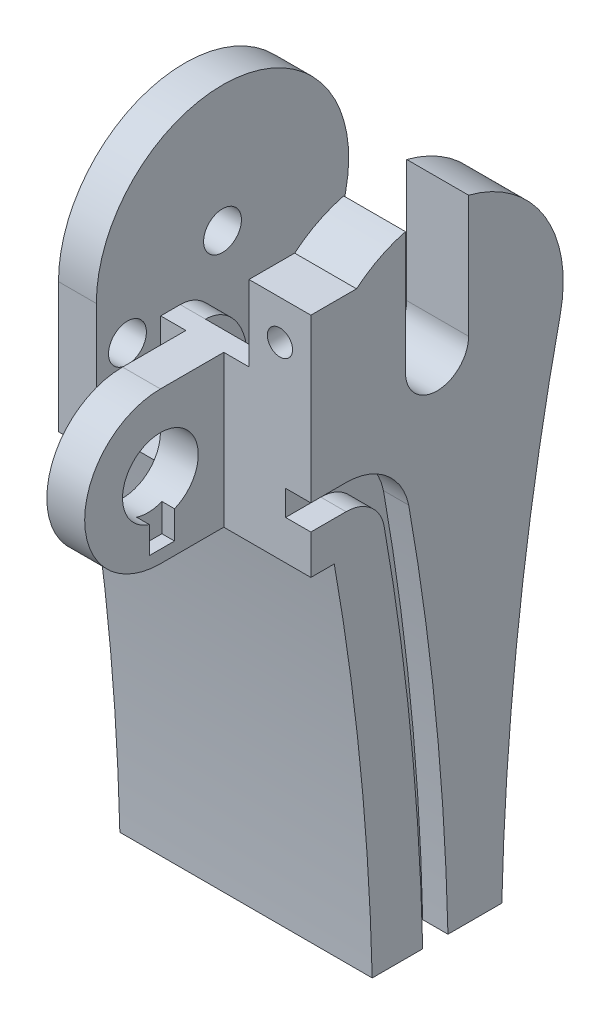
SolidWorks part; units mm, degrees
ref_plane "Front Plane" through (0, 0, 0) normal (0, 0, 1) x (1, 0, 0)
ref_plane "Top Plane" through (0, 0, 0) normal (0, 1, 0) x (1, 0, 0)
ref_plane "Right Plane" through (0, 0, 0) normal (1, 0, 0) x (0, 0, -1)
sketch "Sketch1" plane through (0, 0, 0) normal (1, 0, 0) x (0, 0, -1)
  arc A0 (9.7654, 20.1165) -> (-9.7654, 20.1165) centre (0, 22.2701) ccw
  arc A1 (-7.8874, -56.3924) -> (7.8874, -56.3924) centre (0, -57.7299) ccw
  arc A2 (-7.8874, -56.3924) -> (-9.7654, 20.1165) centre (-205.0724, -22.9549) ccw
  circle A3 centre (0, 22.2701) radius 1.5
  arc A4 (9.7654, 20.1165) -> (7.8874, -56.3924) centre (205.0724, -22.9549) ccw
  circle A5 centre (0, -57.7299) radius 2.5
extrude "Boss-Extrude1" add sketch "Sketch1" along normal blind 20
sketch "Sketch2" plane through (0, 0, 0) normal (0, 0, 1) x (1, 0, 0)
  line L1 (0, -65.7299) -> (8.1, -65.7299)
  line L2 (0, -65.7299) -> (0, -45.7299)
  line L3 (0, -45.7299) -> (8.1, -45.7299)
  line L4 (8.1, -65.7299) -> (8.1, -45.7299)
  line L5 (20, -65.7299) -> (14.8, -65.7299)
  line L6 (20, -65.7299) -> (20, -45.7299)
  line L7 (20, -45.7299) -> (14.8, -45.7299)
  line L8 (14.8, -65.7299) -> (14.8, -45.7299)
  line L11 (3, 32.2701) -> (8.1, 32.2701)
  line L12 (3, 32.2701) -> (3, 12.2701)
  line L13 (3, 12.2701) -> (8.1, 12.2701)
  line L14 (8.1, 32.2701) -> (8.1, 12.2701)
extrude "Cut-Extrude1" cut sketch "Sketch2" against normal blind 20 and the other way blind 20
sketch "Sketch3" plane through (8.1, 0, 0) normal (-1, 0, 0) x (0, 0, 1)
  line L0 (8.5, 22.2701) -> (8.5, 40.9095)
  line L1 (8.5, 40.9095) -> (-17.5287, 40.9095)
  line L2 (-17.5287, 40.9095) -> (-17.5287, 13.7701)
  line L3 (0, 13.7701) -> (-17.5287, 13.7701)
  arc A0 (0, 13.7701) -> (8.5, 22.2701) centre (0, 22.2701) ccw
extrude "Cut-Extrude2" cut sketch "Sketch3" against normal blind 9
sketch "Sketch4" plane through (8.1, 0, 0) normal (-1, 0, 0) x (0, 0, 1)
  line L0 (8.5, 27.5379) -> (8.2838, 12.7416)
  line L1 (8.2838, 12.7416) -> (10.2838, 12.7416)
  line L2 (10.2838, 12.7416) -> (10.2838, 27.5379)
  line L3 (10.2838, 27.5379) -> (8.5, 27.5379)
  arc A0 (9.7654, 20.1165) -> (6.3734, -45.7299) centre (205.0724, -22.9549) ccw construction
extrude "Boss-Extrude2" add sketch "Sketch4" against normal through all
sketch "Sketch5" plane through (8.1, 0, 0) normal (-1, 0, 0) x (0, 0, 1)
  line L4 (8.1452, 11.9686) -> (8.4478, 23.9686)
  line L6 (15.0224, 23.9686) -> (9.8547, 23.9686)
  line L8 (8.1452, 11.9686) -> (15.0224, 11.9686)
  line L9 (8.5, 27.5379) -> (8.4045, 20.9993) construction
  line L10 (8.4478, 23.9686) -> (9.8547, 23.9686)
  circle A2 centre (15.0224, 17.9686) radius 3
  arc A5 (15.0224, 11.9686) -> (15.0224, 23.9686) centre (15.0224, 17.9686) ccw
  arc A6 (9.7654, 20.1165) -> (-9.7654, 20.1165) centre (0, 22.2701) ccw construction
  arc A7 (9.7654, 20.1165) -> (6.3734, -45.7299) centre (205.0724, -22.9549) ccw construction
extrude "Boss-Extrude3" add sketch "Sketch5" against normal blind 5
sketch "Sketch12" plane through (13.1, 0, 0) normal (1, 0, 0) x (0, 0, -1)
  line L2 (-13.9029, 14.9686) -> (-13.9029, 12.9686)
  line L4 (-15.9029, 14.9686) -> (-15.9029, 15.2943)
  line L5 (-15.9029, 15.2943) -> (-13.9029, 15.2943)
  line L6 (-13.9029, 12.9686) -> (-15.9029, 12.9686)
  line L7 (-13.9029, 14.9686) -> (-13.9029, 15.2943)
  line L11 (-15.9029, 14.9686) -> (-15.9029, 12.9686)
extrude "Cut-Extrude6" cut sketch "Sketch12" against normal blind 1
sketch "Sketch13" plane through (17.1, 0, 0) normal (-1, 0, 0) x (0, 0, 1)
  circle A0 centre (0, 22.2701) radius 2.5
extrude "Cut-Extrude7" cut sketch "Sketch13" against normal blind 4
sketch "Sketch15" plane through (0, 0, 0) normal (-1, 0, 0) x (0, 0, 1)
  line L0 (10, 22.2701) -> (10, 11.9686)
  line L1 (8.1452, 11.9686) -> (15.0224, 11.9686) construction
  line L2 (10, 11.9686) -> (8.1452, 11.9686)
  line L3 (10, 22.2701) -> (7.5957, 11.9686)
  line L4 (7.5957, 11.9686) -> (8.1452, 11.9686)
  arc A0 (9.7654, 20.1165) -> (-9.7654, 20.1165) centre (0, 22.2701) ccw construction
extrude "Boss-Extrude4" add sketch "Sketch15" against normal blind 3
sketch "Sketch16" plane through (20, 0, 0) normal (1, 0, 0) x (0, 0, -1)
  line L0 (-10.2838, 23.9686) -> (-9.8547, 23.9686)
  line L1 (-10.2838, 23.9686) -> (-10.2838, 27.5379)
  line L2 (-10.2838, 27.5379) -> (-8.5, 27.5379) construction
  line L3 (-10.2838, 12.7416) -> (-10.2838, 27.5379) construction
  line L4 (-10.2838, 27.5379) -> (-8.5, 27.5379)
  arc A0 (-8.5, 27.5379) -> (-9.8547, 23.9686) centre (0, 22.2701) ccw
extrude "Cut-Extrude9" cut sketch "Sketch16" against normal blind 3
sketch "Sketch17" plane through (0, 0, 10.2838) normal (0, 0, 1) x (1, 0, 0)
  line L1 (17.1, 27.5379) -> (8.1, 27.5379)
  line L2 (17.1, 27.5379) -> (17.1, 23.9686)
  line L3 (17.1, 23.9686) -> (8.1, 23.9686)
  line L4 (8.1, 27.5379) -> (8.1, 23.9686)
extrude "Cut-Extrude11" cut sketch "Sketch17" against normal blind 3
sketch "Sketch18" plane through (13.1, 0, 0) normal (1, 0, 0) x (0, 0, -1)
  line L1 (-10.2838, 12.7416) -> (-4.5128, 12.7416)
  line L2 (-10.2838, 12.7416) -> (-10.2838, 11.9686)
  line L3 (-10.2838, 11.9686) -> (-4.5128, 11.9686)
  line L4 (-4.5128, 12.7416) -> (-4.5128, 11.9686)
extrude "Boss-Extrude5" add sketch "Sketch18" along normal through all and the other way blind 1
sketch "Sketch19" plane through (0, 12.2701, 0) normal (0, 1, 0) x (1, 0, 0)
  line L1 (8.1, -8.1989) -> (3, -8.1989)
  line L2 (8.1, -8.1989) -> (8.1, 8.1989)
  line L3 (8.1, 8.1989) -> (3, 8.1989)
  line L4 (3, -8.1989) -> (3, 8.1989)
extrude "Cut-Extrude12" cut sketch "Sketch19" against normal up to surface (0.3015 mm away) up to face at (1.5, 11.9686, 9.0726)
sketch "Sketch20" plane through (17.1, 0, 0) normal (-1, 0, 0) x (0, 0, 1)
  line L1 (2.5, 22.2701) -> (-2.5, 22.2701)
  line L2 (2.5, 22.2701) -> (2.5, 34.6894)
  line L3 (2.5, 34.6894) -> (-2.5, 34.6894)
  line L4 (-2.5, 22.2701) -> (-2.5, 34.6894)
  circle A0 centre (0, 22.2701) radius 2.5 construction
extrude "Cut-Extrude13" cut sketch "Sketch20" against normal blind 10
sketch "Sketch21" plane through (17.1, 0, 0) normal (-1, 0, 0) x (0, 0, 1)
  line L1 (-8.4732, 13.7701) -> (0.2785, 12.274)
  line L3 (2.5, 22.2701) -> (2.5, 31.9526)
  line L5 (-2.5, 22.2701) -> (-2.5, 31.9526)
  arc A0 (0.2785, 12.274) -> (2.5, 31.9526) centre (0, 22.2701) ccw
  arc A1 (-2.5, 22.2701) -> (2.5, 22.2701) centre (0, 22.2701) ccw
  arc A2 (-2.5, 31.9526) -> (-9.7654, 20.1165) centre (0, 22.2701) ccw
  arc A7 (-8.4732, 13.7701) -> (-9.7654, 20.1165) centre (-205.0724, -22.9549) ccw
extrude "Boss-Extrude6" add sketch "Sketch21" along normal blind 2
sketch "Sketch23" plane through (0, 0, 10.2838) normal (0, 0, 1) x (1, 0, 0)
  line L1 (15.1, 23.9686) -> (20, 23.9686)
  line L2 (15.1, 23.9686) -> (15.1, 29.9686)
  line L3 (15.1, 29.9686) -> (20, 29.9686)
  line L4 (20, 23.9686) -> (20, 29.9686)
extrude "Boss-Extrude7" add sketch "Sketch23" against normal blind 4
sketch "Sketch22" plane through (0, 0, 10.2838) normal (0, 0, 1) x (1, 0, 0)
  circle A1 centre (17.55, 26.8701) radius 1
extrude "Cut-Extrude15" cut sketch "Sketch22" against normal blind 8
sketch "Sketch24" plane through (8.1, 0, 0) normal (-1, 0, 0) x (0, 0, 1)
  line L0 (5.1478, 19.7374) -> (5.1478, 15.5063)
  line L2 (8.4478, 23.9686) -> (8.4478, 15.5063)
  line L3 (8.4478, 15.5063) -> (5.1478, 15.5063)
  arc A0 (0, 13.7701) -> (8.3673, 20.7738) centre (0, 22.2701) ccw construction
  ellipse E0 centre (8.4478, 19.7374) end of major axis (8.4478, 15.5063) minor radius 3.3 (8.4478, 23.9686) -> (5.1478, 19.7374) ccw
extrude "Boss-Extrude8" add sketch "Sketch24" against normal blind 2
sketch "Sketch14" plane through (0, 0, 0) normal (-1, 0, 0) x (0, 0, 1)
  circle A3 centre (7.5326, 18.3318) radius 1.5
extrude "Cut-Extrude8" cut sketch "Sketch14" against normal up to surface (10.1 mm away) up to face at (10.1, 20.14, 6.7306)
sketch "Sketch25" plane through (8.1, 0, 0) normal (-1, 0, 0) x (0, 0, 1)
  line L0 (12, -45.7299) -> (8.3462, -36.9607)
  line L1 (-12, -45.7299) -> (-12, -57.7299)
  line L2 (12, -45.7299) -> (12, -57.7299)
  line L3 (-12, -45.7299) -> (-8.3462, -36.9607)
  line L5 (2.5, -53.2274) -> (2.5, -45.7299)
  line L7 (-2.5, -53.2274) -> (-2.5, -45.7299)
  arc A0 (-2.5, -53.2274) -> (2.5, -53.2274) centre (0, -57.7299) ccw
  arc A1 (-12, -57.7299) -> (12, -57.7299) centre (0, -57.7299) ccw
  arc A2 (2.5, -45.7299) -> (8.3462, -36.9607) centre (0, -37.7299) ccw
  arc A4 (-8.3462, -36.9607) -> (-2.5, -45.7299) centre (0, -37.7299) ccw
extrude "Cut-Extrude17" cut sketch "Sketch25" against normal blind 2 and the other way up to surface (8.1 mm away) other way up to face at (0, 18.3318, 9.0326)
sketch "Sketch26" plane through (20, 0, 0) normal (1, 0, 0) x (0, 0, -1)
  line L0 (-10.2838, 11.9686) -> (-10.2838, 29.9686) construction
  line L1 (-7.21, 15.0854) -> (-10.2838, 15.0854)
  line L3 (-7.21, 17.0854) -> (-10.2838, 17.0854)
  line L4 (-10.2838, 15.0854) -> (-10.2838, 17.0854)
  line L8 (-1.6082, -37.73) -> (0.397, -37.73)
  arc A0 (-4.2066, 12.6671) -> (-7.21, 15.0854) centre (-7.21, 12.0113) ccw
  arc A1 (-2.2434, 13.0504) -> (-7.21, 17.0854) centre (-7.21, 12.0113) ccw
  arc A2 (-2.3994, -46.1854) -> (-4.2066, 12.6671) centre (-205.0724, -22.9549) ccw
  arc A3 (-1.6082, -37.73) -> (-4.2066, 12.6671) centre (-205.0724, -22.9549) ccw
  circle A4 centre (-7.21, 12.0113) radius 5.0741 construction
  circle A5 centre (-7.21, 12.0113) radius 3.0741 construction
  arc A6 (-0.4124, -46.4131) -> (-2.2373, 13.0163) centre (-205.0724, -22.9549) ccw
  arc A7 (0.397, -37.73) -> (-2.2434, 13.0504) centre (-205.0724, -22.9549) ccw
  dimension "D3" = 2
  dimension "D1" = 4
  dimension "D2" = 6
extrude "Cut-Extrude18" cut sketch "Sketch26" against normal blind 2
sketch "Sketch29" plane through (20, 0, 0) normal (1, 0, 0) x (0, 0, -1)
  line L1 (8, -37.7299) -> (8.1403, -37.7299)
  line L2 (-15.7549, -37.7299) -> (-8, -37.7299)
  line L3 (-15.7549, -37.7299) -> (-15.7549, -45.9375)
  line L4 (-15.7549, -45.9375) -> (8.1403, -45.9375)
  line L5 (8.1403, -37.7299) -> (8.1403, -45.9375)
  arc A0 (-8, -37.7299) -> (8, -37.7299) centre (0, -37.7299) ccw
extrude "Cut-Extrude20" cut sketch "Sketch29" against normal up to surface (5.2 mm away) up to face at (14.8, -57.7299, -2.5)
sketch "Sketch30" plane through (0, 0, 10.2838) normal (0, 0, 1) x (1, 0, 0)
  line L1 (13.1, 11.9686) -> (20, 11.9686)
  line L2 (13.1, 11.9686) -> (13.1, 31.9686)
  line L3 (13.1, 31.9686) -> (20, 31.9686)
  line L4 (20, 11.9686) -> (20, 31.9686)
extrude "Cut-Extrude21" cut sketch "Sketch30" against normal up to surface (0.2838 mm away) up to face at (1.5, 17.1194, 10)
sketch "Sketch31" plane through (0, 23.9686, 0) normal (0, 1, 0) x (1, 0, 0)
  line L0 (8.1, -15.0224) -> (8.1, -8.4478) construction
  line L1 (8.1, -10) -> (10.1, -10)
  line L2 (8.1, -10) -> (8.1, -21.0224)
  line L3 (8.1, -21.0224) -> (10.1, -21.0224)
  line L4 (10.1, -10) -> (10.1, -21.0224)
  line L5 (8.1, -21.0224) -> (13.1, -21.0224) construction
extrude "Cut-Extrude22" cut sketch "Sketch31" against normal up to next
sketch "Sketch32" plane through (8.1, 0, 0) normal (-1, 0, 0) x (0, 0, 1)
  line L0 (-8.4732, 13.7701) -> (-8.4732, 5.4011)
  line L2 (5.1478, 15.5063) -> (-8.4732, 5.4011)
  line L5 (5.1478, 15.5063) -> (-8.4732, 13.7701)
extrude "Cut-Extrude23" cut sketch "Sketch32" against normal blind 7
sketch "Sketch33" plane through (20, 0, 0) normal (1, 0, 0) x (0, 0, -1)
  line L2 (-9.3048, -22.9549) -> (-9.3048, -27.9549)
  line L3 (-9.3048, -27.9549) -> (8.8924, -27.9549)
  line L4 (8.8924, -22.9549) -> (8.8924, -27.9549)
  line L6 (-9.3048, -22.9549) -> (-9.3048, -17.9549)
  line L7 (-9.3048, -17.9549) -> (8.8924, -17.9549)
  line L8 (8.8924, -22.9549) -> (8.8924, -17.9549)
extrude "Cut-Extrude24" cut sketch "Sketch33" against normal through all
sketch "Sketch34" plane through (20, 0, 0) normal (1, 0, 0) x (0, 0, -1)
  line L1 (-35.7784, -82.5503) -> (24.748, -82.5503)
  line L2 (-35.7784, -82.5503) -> (-35.7784, -24.0951)
  line L3 (-35.7784, -24.0951) -> (24.748, -24.0951)
  line L4 (24.748, -82.5503) -> (24.748, -24.0951)
extrude "Cut-Extrude25" cut sketch "Sketch34" against normal through all
